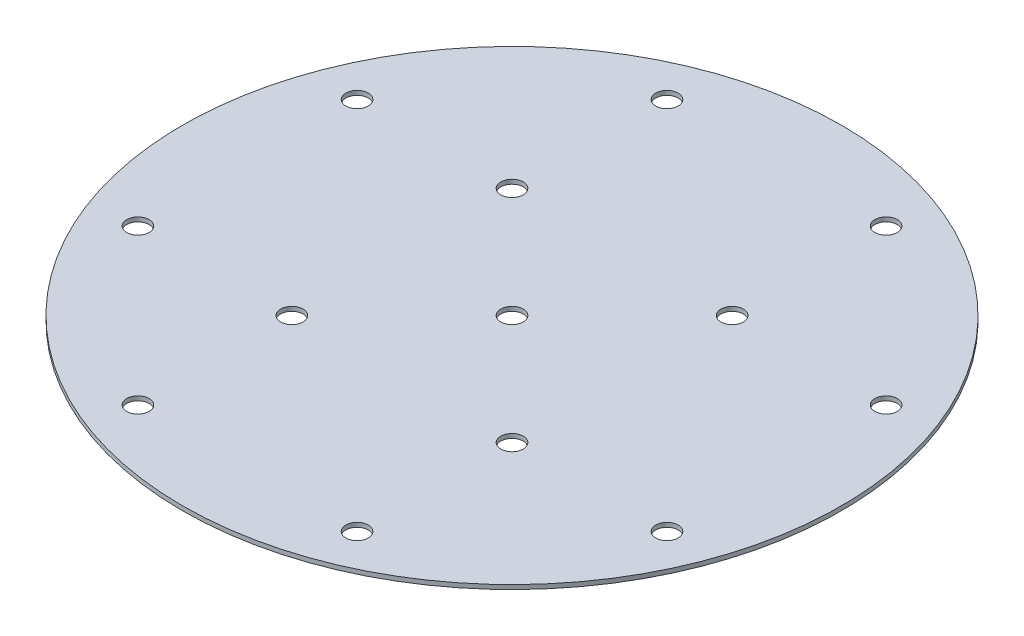
SolidWorks part; units mm, degrees
material "6061-T6 (SS)"
ref_plane "Front Plane" through (0, 0, 0) normal (0, 0, 1) x (1, 0, 0)
ref_plane "Top Plane" through (0, 0, 0) normal (0, 1, 0) x (1, 0, 0)
ref_plane "Right Plane" through (0, 0, 0) normal (1, 0, 0) x (0, 0, -1)
sketch "Sketch2" plane through (0, 0, 0) normal (1, 0, 0) x (0, 0, -1)
  line L0 (0, 0) -> (-76.2, 0)
  line L1 (-76.2, 0) -> (-76.2, 1)
  line L2 (-76.2, 1) -> (0, 1)
  line L5 (0, 1) -> (0, 0)
  dimension "D1" = 76.2
  dimension "D2" = 1
ref_axis "Axis1" through (0, -0.05, 0) along (0, 1, 0)
revolve "Revolve1" add sketch "Sketch2" angle 360 about axis through (0, -0.05, 0) along (0, 1, 0)
hole_wizard "#6 (0.204) Diameter Hole1" positions "Sketch6" profile "Sketch7" hole size "#6" standard "ANSI Inch" end condition through all
sketch "Sketch6" plane through (0, 1, 0) normal (0, 1, 0) x (1, 0, 0)
  line L0 (0, 0) -> (-53.438, 129.0108) construction
  line L2 (0, 0) -> (0, 109.0908) construction
  line L3 (0, 0) -> (-70.3996, 29.1605) construction
  line L4 (0, 0) -> (-47.7784, 47.7784) construction
  circle A0 centre (0, 0) radius 76.2 construction
  point P0 (-25.3336, 61.1608)
  point P11 (264.7437, 73.7878)
  point P20 (-61.1608, 25.3336)
  point P22 (-25.4558, 25.4558)
  dimension "D1" = 22.5
  dimension "D2" = 66.2
  dimension "D3" = 66.2
  dimension "D4" = 45
  dimension "D6" = 22.5
  dimension "D5" = 36
sketch "Sketch7" plane through (-25.3336, 1, -61.1608) normal (1, 0, 0) x (0, 0, 1)
  line L0 (0, 0) -> (0, 1)
  line L1 (0, 1) -> (2.5908, 1)
  line L2 (2.5908, 1) -> (2.5908, 0)
  line L5 (2.5908, 0) -> (0, 0)
  line L11 (0, -6.35) -> (0, 107.95) construction
  dimension "Thru Hole Dia." = 5.1816
  dimension "Thru Hole Depth" = 1
pattern_circular "CirPattern3" count 4 over 360 about axis through (0, -0.05, 0) along (0, 1, 0) of "#6 (0.204) Diameter Hole1"
hole_wizard "#6 (0.204) Diameter Hole2" positions "Sketch8" profile "Sketch9" hole size "#6" standard "ANSI Inch" end condition through all
sketch "Sketch8" plane through (0, 1, 0) normal (0, 1, 0) x (1, 0, 0)
  line L0 (0, 0) -> (106.3094, -1.7118) construction
  point P7 (0, 0)
sketch "Sketch9" plane through (0, 1, 0) normal (1, 0, 0) x (0, 0, 1)
  line L0 (0, 0) -> (0, 1)
  line L1 (0, 1) -> (2.5908, 1)
  line L2 (2.5908, 1) -> (2.5908, 0)
  line L5 (2.5908, 0) -> (0, 0)
  line L11 (0, -6.35) -> (0, 107.95) construction
  dimension "Thru Hole Dia." = 5.1816
  dimension "Thru Hole Depth" = 1
equation "\"TubeDiameter\"= 6.000in"
equation "\"D1@Sketch2\"=\"TubeDiameter\"/2"
equation "\"D2@Sketch6\"=\"TubeDiameter\"/2-10mm"
